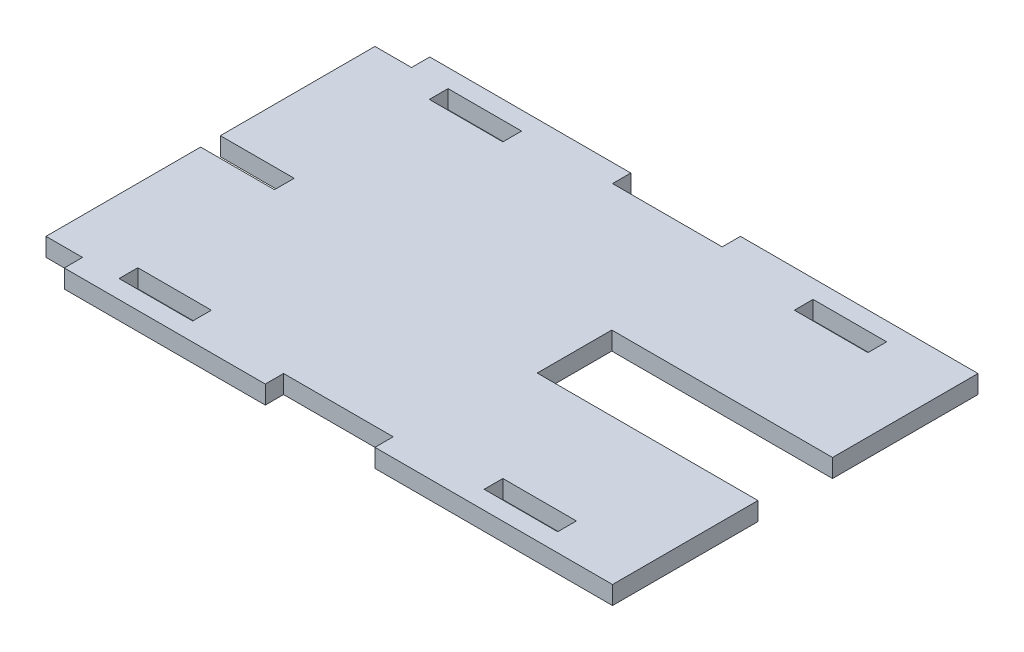
SolidWorks part; units mm, degrees
ref_plane "Front Plane" through (0, 0, 0) normal (0, 0, 1) x (1, 0, 0)
ref_plane "Top Plane" through (0, 0, 0) normal (0, 1, 0) x (1, 0, 0)
ref_plane "Right Plane" through (0, 0, 0) normal (1, 0, 0) x (0, 0, -1)
sketch "Sketch1" plane through (0, 0, 0) normal (0, 1, 0) x (1, 0, 0)
  line L0 (0, 63.5) -> (203.2, 63.5) construction
  line L1 (0, 0) -> (203.2, 0)
  line L2 (0, 0) -> (0, 60.071)
  line L3 (0, 127) -> (203.2, 127)
  line L4 (203.2, 0) -> (203.2, 50.546)
  line L5 (202.946, 76.2) -> (126.746, 76.2) construction
  line L7 (202.946, 50.8) -> (126.746, 50.8) construction
  line L8 (126.746, 76.2) -> (126.746, 50.8) construction
  line L9 (203.2, 76.454) -> (126.492, 76.454)
  line L10 (126.492, 76.454) -> (126.492, 50.546)
  line L11 (203.2, 50.546) -> (126.492, 50.546)
  line L12 (203.2, 66.929) -> (203.2, 60.071)
  line L13 (0, 66.929) -> (25.654, 66.929)
  line L14 (0, 66.675) -> (25.4, 66.675) construction
  line L16 (0, 60.325) -> (25.4, 60.325) construction
  line L17 (25.4, 66.675) -> (25.4, 60.325) construction
  line L22 (25.654, 66.929) -> (25.654, 60.071)
  line L23 (0, 60.071) -> (25.654, 60.071)
  line L27 (0, 66.929) -> (0, 127)
  line L28 (203.2, 76.454) -> (203.2, 127)
  line L29 (203.2, 60.071) -> (203.2, 66.929)
  line L30 (203.2, 76.454) -> (203.2, 50.546) construction
  line L31 (202.946, 76.2) -> (202.946, 50.8) construction
  dimension "D1" = 203.2
  dimension "D2" = 127
  dimension "D4" = 25.4
  dimension "D5" = 76.2
  dimension "D9" = 25.4
  dimension "D10" = 6.35
  dimension "D6" = 0.254
  dimension "D11" = 0.254
extrude "Boss-Extrude1" add sketch "Sketch1" along normal blind 6.35 contours L28 L3 L27 L13 L22 L23 L2 L1 L4 L11 L10 L9 region at (96.9444, 0, -63.5)
sketch "Sketch4" plane through (0, 6.35, 0) normal (0, 1, 0) x (1, 0, 0)
  line L1 (25.4762, 6.4262) -> (50.8762, 6.4262) construction
  line L2 (25.4762, 6.4262) -> (25.4762, 12.7762) construction
  line L3 (25.4762, 12.7762) -> (50.8762, 12.7762) construction
  line L4 (50.8762, 6.4262) -> (50.8762, 12.7762) construction
  line L6 (101.6, 0) -> (101.6, 127) construction
  line L8 (0, 63.5) -> (196.85, 63.5) construction
  line L9 (0, 66.929) -> (0, 60.071)
  line L16 (152.3238, 6.4262) -> (152.3238, 12.7762) construction
  line L17 (177.7238, 12.7762) -> (152.3238, 12.7762) construction
  line L18 (177.7238, 6.4262) -> (177.7238, 12.7762) construction
  line L19 (177.7238, 6.4262) -> (152.3238, 6.4262) construction
  line L20 (177.7238, 120.5738) -> (152.3238, 120.5738) construction
  line L21 (177.7238, 120.5738) -> (177.7238, 114.2238) construction
  line L22 (177.7238, 114.2238) -> (152.3238, 114.2238) construction
  line L23 (152.3238, 120.5738) -> (152.3238, 114.2238) construction
  line L24 (50.8762, 120.5738) -> (50.8762, 114.2238) construction
  line L25 (25.4762, 114.2238) -> (50.8762, 114.2238) construction
  line L26 (25.4762, 120.5738) -> (25.4762, 114.2238) construction
  line L27 (25.4762, 120.5738) -> (50.8762, 120.5738) construction
  line L28 (50.9524, 120.65) -> (50.9524, 114.1476)
  line L29 (25.4, 114.1476) -> (50.9524, 114.1476)
  line L30 (25.4, 120.65) -> (25.4, 114.1476)
  line L31 (25.4, 120.65) -> (50.9524, 120.65)
  line L32 (177.8, 120.65) -> (152.2476, 120.65)
  line L33 (152.2476, 120.65) -> (152.2476, 114.1476)
  line L34 (177.8, 114.1476) -> (152.2476, 114.1476)
  line L35 (177.8, 120.65) -> (177.8, 114.1476)
  line L36 (25.4, 6.35) -> (50.9524, 6.35)
  line L37 (50.9524, 6.35) -> (50.9524, 12.8524)
  line L38 (25.4, 12.8524) -> (50.9524, 12.8524)
  line L39 (25.4, 6.35) -> (25.4, 12.8524)
  line L40 (152.2476, 6.35) -> (152.2476, 12.8524)
  line L41 (177.8, 12.8524) -> (152.2476, 12.8524)
  line L42 (177.8, 6.35) -> (177.8, 12.8524)
  line L43 (177.8, 6.35) -> (152.2476, 6.35)
  line L44 (12.7, 127) -> (12.7, 120.65)
  line L45 (0, 0) -> (12.7, 0)
  line L46 (0, 0) -> (0, 6.35)
  line L47 (0, 6.35) -> (12.7, 6.35)
  line L48 (12.7, 0) -> (12.7, 6.35)
  line L49 (82.55, 0) -> (120.65, 0)
  line L50 (82.55, 0) -> (82.55, 6.35)
  line L51 (82.55, 6.35) -> (120.65, 6.35)
  line L52 (120.65, 0) -> (120.65, 6.35)
  line L53 (0, 120.65) -> (12.7, 120.65)
  line L54 (0, 127) -> (0, 120.65)
  line L55 (0, 127) -> (12.7, 127)
  line L56 (120.65, 127) -> (120.65, 120.65)
  line L57 (82.55, 120.65) -> (120.65, 120.65)
  line L58 (82.55, 127) -> (82.55, 120.65)
  line L59 (82.55, 127) -> (120.65, 127)
  line L60 (0, 66.929) -> (25.654, 66.929) construction
  line L61 (0, 60.071) -> (25.654, 60.071) construction
  line L62 (0, 0) -> (0, 60.071) construction
  line L63 (0, 0) -> (203.2, 0) construction
  point P10 (0, 0)
  point P17 (0, 0)
  point P20 (0, 0)
  point P73 (0, 0)
  dimension "D2" = 25.4
  dimension "D3" = 6.35
  dimension "D8" = 6.35
  dimension "D9" = 12.7
  dimension "D10" = 6.35
  dimension "D11" = 6.35
  dimension "D12" = 38.1
  dimension "D13" = 25.4
  dimension "D4" = 0.0762
  dimension "D5" = 0.0762
  dimension "D6" = 0.0762
  dimension "D7" = 0.0762
extrude "Cut-Extrude1" cut sketch "Sketch4" against normal through all contours L53 L44 | L31 L30 L29 L28 | L58 L57 L56 | L35 L32 L33 L34 | L43 L42 L41 L40 | L52 L51 L50 | L39 L36 L37 L38 | L48 L47 region at (38.1762, 6.35, -117.3988) region at (165.0238, 6.35, -117.3988) region at (38.1762, 6.35, -9.6012) region at (165.0238, 6.35, -9.6012) region at (6.35, 6.35, -123.825) region at (6.35, 6.35, -3.175) region at (101.6, 6.35, -3.175) region at (101.6, 6.35, -123.825)
